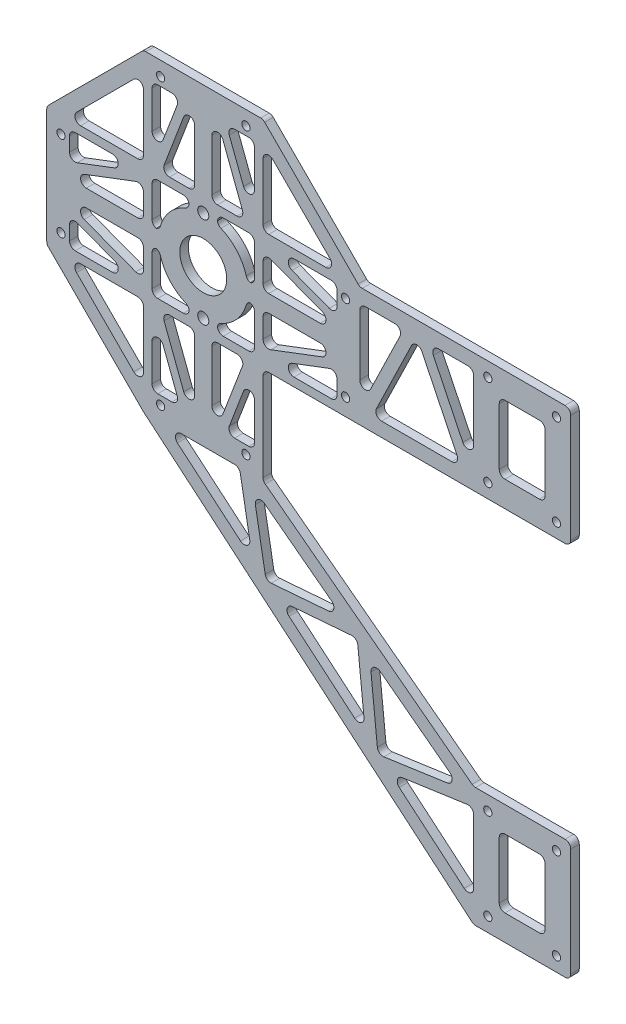
SolidWorks part; units mm, degrees
material "Thornel Mat VMA"
ref_plane "前视基准面" through (0, 0, 0) normal (0, 0, 1) x (1, 0, 0)
ref_plane "上视基准面" through (0, 0, 0) normal (0, 1, 0) x (1, 0, 0)
ref_plane "右视基准面" through (0, 0, 0) normal (1, 0, 0) x (0, 0, -1)
other "Configuration Table"
sketch "草图1" plane through (0, 0, 0) normal (0, 0, 1) x (1, 0, 0)
  line L0 (100, -1053.4194) -> (100, 48946.5806) construction
  line L1 (124.12, -1022.8771) -> (124.12, 48977.1229) construction
  line L2 (0, -1000) -> (0, 49000) construction
  line L3 (0, 16) -> (124.12, 16) construction
  line L4 (124.12, -16) -> (0, -16) construction
  line L6 (-15, 21) -> (129.12, 21) construction
  line L7 (-15, 21) -> (-15, -21) construction
  line L8 (-15, -21) -> (129.12, -21) construction
  line L9 (129.12, 21) -> (129.12, -21) construction
  line L18 (-1000, 50) -> (49000, 50) construction
  line L19 (-1000, -50) -> (49000, -50) construction
  line L20 (-50, -995.7067) -> (-50, 49004.2933) construction
  line L21 (50, -1002.265) -> (50, 48997.735) construction
  line L22 (0, 0) -> (15, 50) construction
  line L23 (100, -116) -> (124.12, -116) construction
  line L24 (100, -148) -> (124.12, -148) construction
  line L25 (21, 55) -> (-21, 55) construction
  line L26 (-55, 21) -> (-15, 21) construction
  line L27 (-55, 21) -> (-55, -21) construction
  line L28 (-55, -21) -> (-15, -21) construction
  line L29 (-15, 21) -> (-15, -21) construction
  line L30 (21, 55) -> (21, 15) construction
  line L31 (21, 15) -> (-21, 15) construction
  line L32 (-21, 55) -> (-21, 15) construction
  line L33 (55, -21) -> (55, 21) construction
  line L34 (55, -21) -> (15, -21) construction
  line L35 (15, -21) -> (15, 21) construction
  line L36 (55, 21) -> (15, 21) construction
  line L37 (-21, -55) -> (21, -55) construction
  line L38 (-21, -55) -> (-21, -15) construction
  line L39 (-21, -15) -> (21, -15) construction
  line L40 (21, -55) -> (21, -15) construction
  line L41 (0, 0) -> (-15, 21) construction
  line L42 (-55, 21) -> (-55, -21)
  line L43 (-55, -21) -> (-21, -55)
  line L44 (-21, -55) -> (95, -153)
  line L45 (95, -153) -> (129.12, -153)
  line L46 (129.12, -153) -> (129.12, 21)
  line L47 (129.12, 21) -> (55, 21)
  line L48 (55, 21) -> (21, 55)
  line L49 (21, 55) -> (-21, 55)
  line L50 (-21, 55) -> (-55, 21)
  circle A0 centre (0, 0) radius 16 construction
  circle A1 centre (0, 16) radius 1.95
  circle A2 centre (0, -16) radius 1.95
  circle A3 centre (0, 0) radius 8.25
  circle A4 centre (100, 16) radius 1.45
  circle A5 centre (100, -16) radius 1.45
  circle A6 centre (124.12, -16) radius 1.45
  circle A7 centre (124.12, 16) radius 1.45
  circle A8 centre (-15, 50) radius 1.45
  circle A9 centre (15, 50) radius 1.45
  circle A10 centre (50, 15) radius 1.45
  circle A11 centre (50, -15) radius 1.45
  circle A12 centre (15, -50) radius 1.45
  circle A13 centre (-15, -50) radius 1.45
  circle A14 centre (-50, -15) radius 1.45
  circle A15 centre (-50, 15) radius 1.45
  circle A16 centre (100, -116) radius 1.45
  circle A17 centre (124.12, -116) radius 1.45
  circle A18 centre (100, -148) radius 1.45
  circle A19 centre (124.12, -148) radius 1.45
  dimension "D1" = 3.9
  dimension "D2" = 32
  dimension "D3" = 16.5
  dimension "D6" = 2.9
  dimension "D7" = 15
  dimension "D17" = 4
  dimension "D15" = 2.9
  dimension "D16" = 30
  dimension "D4" = 100
  dimension "D5" = 24.12
  dimension "D8" = 5
  dimension "D9" = 5
  dimension "D10" = 5
  dimension "D11" = 50
  dimension "D12" = 50
  dimension "D13" = 50
  dimension "D14" = 50
  dimension "D18" = 32
  dimension "D19" = 100
  dimension "D20" = 5
  dimension "D22" = 5
  dimension "D23" = 5
  dimension "D21" = 4
extrude "凸台-拉伸1" add sketch "草图1" along normal blind 3
sketch "草图2" plane through (0, 0, 3) normal (0, 0, 1) x (1, 0, 0)
  line L0 (-21, 55) -> (-21, -55) construction
  line L1 (-55, -21) -> (129.12, -21) construction
  line L2 (129.12, -153) -> (129.12, 21) construction
  line L3 (127.917, 21) -> (-55, 21) construction
  line L4 (21, 55) -> (21, -55) construction
  line L5 (21, -55) -> (-21, -55) construction
  line L6 (129.12, -111) -> (95, -111) construction
  line L7 (95, -111) -> (95, -153) construction
  line L8 (95, -111) -> (95, -21) construction
  line L9 (21, -55) -> (95, -111) construction
  line L10 (129.12, -21) -> (21, -21)
  line L11 (21, -21) -> (21, -55)
  line L12 (21, -55) -> (95, -111)
  line L13 (95, -111) -> (129.12, -111)
  line L14 (129.12, -111) -> (129.12, -21)
  line L15 (-47.9289, -21) -> (-21, -47.9289)
  line L16 (-21, -47.9289) -> (-21, -21)
  line L17 (-21, -21) -> (-47.9289, -21)
  line L18 (-55, -21) -> (-21, -55) construction
  line L19 (-21, 21) -> (-21, 47.9289)
  line L20 (-21, 47.9289) -> (-47.9289, 21)
  line L21 (-47.9289, 21) -> (-21, 21)
  line L22 (21, 21) -> (47.9289, 21)
  line L23 (47.9289, 21) -> (21, 47.9289)
  line L24 (21, 47.9289) -> (21, 21)
  line L25 (0, 0) -> (-21, -21) construction
  line L26 (0, 0) -> (-21, 21) construction
  line L27 (-55, 0) -> (-21, 0) construction
  line L28 (-55, 21) -> (-55, -21) construction
  line L35 (-47, -8.1113) -> (-47, -18)
  line L36 (-47, -18) -> (-21, -18)
  line L37 (-21, -18) -> (-47, -8.1113)
  line L38 (-21, -14.7903) -> (-52, -3)
  line L39 (-52, -3) -> (-21, -3)
  line L40 (-21, -3) -> (-21, -14.7903)
  line L41 (-52, 3) -> (-21, 3)
  line L42 (-21, 14.7903) -> (-52, 3)
  line L43 (-21, 3) -> (-21, 14.7903)
  line L44 (-47, 18) -> (-21, 18)
  line L45 (-47, 8.1113) -> (-47, 18)
  line L46 (-21, 18) -> (-47, 8.1113)
  line L47 (18, 47) -> (18, 21)
  line L48 (18, 21) -> (8.1113, 47)
  line L49 (8.1113, 47) -> (18, 47)
  line L50 (3, 52) -> (3, 21)
  line L51 (3, 21) -> (14.7903, 21)
  line L52 (14.7903, 21) -> (3, 52)
  line L53 (-3, 21) -> (-14.7903, 21)
  line L54 (-14.7903, 21) -> (-3, 52)
  line L55 (-3, 52) -> (-3, 21)
  line L56 (-18, 21) -> (-8.1113, 47)
  line L57 (-8.1113, 47) -> (-18, 47)
  line L58 (-18, 47) -> (-18, 21)
  line L59 (47, -18) -> (21, -18)
  line L60 (21, -18) -> (47, -8.1113)
  line L61 (47, -8.1113) -> (47, -18)
  line L62 (52, -3) -> (21, -3)
  line L63 (21, -3) -> (21, -14.7903)
  line L64 (21, -14.7903) -> (52, -3)
  line L65 (21, 3) -> (21, 14.7903)
  line L66 (21, 14.7903) -> (52, 3)
  line L67 (52, 3) -> (21, 3)
  line L68 (21, 18) -> (47, 8.1113)
  line L69 (47, 8.1113) -> (47, 18)
  line L70 (47, 18) -> (21, 18)
  line L71 (-18, -47) -> (-18, -21)
  line L72 (-18, -21) -> (-8.1113, -47)
  line L73 (-8.1113, -47) -> (-18, -47)
  line L74 (-3, -52) -> (-3, -21)
  line L75 (-3, -21) -> (-14.7903, -21)
  line L76 (-14.7903, -21) -> (-3, -52)
  line L77 (3, -21) -> (14.7903, -21)
  line L78 (14.7903, -21) -> (3, -52)
  line L79 (3, -52) -> (3, -21)
  line L80 (18, -21) -> (8.1113, -47)
  line L81 (8.1113, -47) -> (18, -47)
  line L82 (18, -47) -> (18, -21)
  line L83 (55, 21) -> (55, -21) construction
  line L84 (-13.2523, -55) -> (95, -146.4545) construction
  line L85 (12.7142, -55) -> (95, -117.2703) construction
  line L86 (-21, -55) -> (95, -153) construction
  line L87 (12.7142, -55) -> (-13.2523, -55)
  line L88 (-13.2523, -55) -> (17.3031, -80.8141)
  line L89 (17.3031, -80.8141) -> (12.7142, -55)
  line L90 (17.4084, -58.5524) -> (22.0838, -84.8529)
  line L91 (22.0838, -84.8529) -> (49.3047, -82.6901)
  line L92 (49.3047, -82.6901) -> (17.4084, -58.5524)
  line L93 (26.4252, -88.5206) -> (54.1032, -86.3214)
  line L94 (54.1032, -86.3214) -> (56.9806, -114.3347)
  line L95 (56.9806, -114.3347) -> (26.4252, -88.5206)
  line L96 (58.4632, -89.6208) -> (61.3837, -118.0545)
  line L97 (61.3837, -118.0545) -> (90.5115, -113.8736)
  line L98 (90.5115, -113.8736) -> (58.4632, -89.6208)
  line L99 (65.4723, -121.5087) -> (95, -117.2703)
  line L100 (95, -117.2703) -> (95, -146.4545)
  line L101 (95, -146.4545) -> (65.4723, -121.5087)
  line L102 (100, -116) -> (100, -148) construction
  line L103 (100, -148) -> (124.12, -148) construction
  line L104 (124.12, -148) -> (124.12, -116) construction
  line L105 (124.12, -116) -> (100, -116) construction
  line L106 (120.12, -120) -> (104, -120)
  line L107 (104, -120) -> (104, -144)
  line L108 (104, -144) -> (120.12, -144)
  line L109 (120.12, -144) -> (120.12, -120)
  line L110 (100, 16) -> (100, -16) construction
  line L111 (100, -16) -> (124.12, -16) construction
  line L112 (124.12, -16) -> (124.12, 16) construction
  line L113 (124.12, 16) -> (100, 16) construction
  line L114 (120.12, 12) -> (104, 12)
  line L115 (104, 12) -> (104, -12)
  line L116 (104, -12) -> (120.12, -12)
  line L117 (120.12, -12) -> (120.12, 12)
  line L118 (95, -21) -> (95, 21) construction
  line L119 (55, 16) -> (95, 16) construction
  line L120 (55, -16) -> (95, -16) construction
  line L121 (55, 16) -> (55, -16)
  line L122 (55, -16) -> (70.5526, 16)
  line L123 (70.5526, 16) -> (55, 16)
  line L124 (75, 16) -> (59.4474, -16)
  line L125 (59.4474, -16) -> (90.5526, -16)
  line L126 (90.5526, -16) -> (75, 16)
  line L127 (79.4474, 16) -> (95, -16)
  line L128 (95, -16) -> (95, 16)
  line L129 (95, 16) -> (79.4474, 16)
  line L130 (-5, 18) -> (-5, 14.9229)
  line L131 (-18, 18) -> (-5, 18)
  line L132 (-18, 18) -> (-18, 3)
  line L133 (-18, -18) -> (-5, -18)
  line L134 (18, 18) -> (18, 3)
  line L135 (-18, 18) -> (18, -18) construction
  line L136 (-18, -18) -> (18, 18) construction
  line L137 (-5, 14.9229) -> (5, 14.9229) construction
  line L138 (5, 14.9229) -> (5, 18)
  line L139 (5, 18) -> (18, 18)
  line L140 (-5, -14.9229) -> (-5, -18)
  line L141 (5, -18) -> (18, -18)
  line L142 (5, -14.9229) -> (5, -18)
  line L143 (-18, 3) -> (-15.4497, 3)
  line L144 (15.4497, 3) -> (18, 3)
  line L145 (18, -3) -> (15.4497, -3)
  line L146 (-15.4497, -3) -> (-18, -3)
  line L147 (-18, -3) -> (-18, -18)
  line L148 (18, -3) -> (18, -18)
  line L149 (129.12, 21) -> (55, 21) construction
  circle A0 centre (124.12, -116) radius 1.45 construction
  arc A1 (-5, 14.9229) -> (-15.4497, 3) centre (0, 0) ccw
  circle A2 centre (-50, -15) radius 1.45 construction
  arc A3 (5, -14.9229) -> (15.4497, -3) centre (0, 0) ccw
  circle A4 centre (0, 16) radius 1.95 construction
  arc A5 (15.4497, 3) -> (5, 14.9229) centre (0, 0) ccw
  arc A6 (-15.4497, -3) -> (-5, -14.9229) centre (0, 0) ccw
  point P169 (127.917, 21)
  dimension "D7" = 3
  dimension "D8" = 3
  dimension "D27" = 5
  dimension "D29" = 15.7383
  dimension "D1" = 5
  dimension "D2" = 5
  dimension "D4" = 90
  dimension "D5" = 3
  dimension "D6" = 3
  dimension "D9" = 3
  dimension "D11" = 5
  dimension "D12" = 5
  dimension "D13" = 4
  dimension "D14" = 4
  dimension "D15" = 40
  dimension "D16" = 40
  dimension "D17" = 40
  dimension "D18" = 4
  dimension "D19" = 4
  dimension "D22" = 5
  dimension "D23" = 5
  dimension "D24" = 4
  dimension "D25" = 4
  dimension "D26" = 3
  dimension "D28" = 36
  dimension "D20" = 4
  dimension "D21" = 4
  dimension "D3" = 3
  dimension "D10" = 4
extrude "切除-拉伸1" cut sketch "草图2" against normal through all
fillet "圆角1" radius 2 123 edges at (21, -55, 1.5) (21, -21, 1.5) (129.12, -21, 1.5) (129.12, 21, 1.5) (55, 21, 1.5) (21, 55, 1.5) (-21, 55, 1.5) (-55, 21, 1.5) (-55, -21, 1.5) (-21, -55, 1.5) (95, -153, 1.5) (129.12, -153, 1.5) (129.12, -111, 1.5) (95, -111, 1.5) (3, -21, 1.5) (14.7903, -21, 1.5) (3, -52, 1.5) (18, -21, 1.5) (18, -47, 1.5) (8.1113, -47, 1.5) (-18, -21, 1.5) (-8.1113, -47, 1.5) (-3, -21, 1.5) (-3, -52, 1.5) (-14.7903, -21, 1.5) (61.3837, -118.0545, 1.5) (58.4632, -89.6208, 1.5) (90.5115, -113.8736, 1.5) (54.1032, -86.3214, 1.5) (56.9806, -114.3347, 1.5) (26.4252, -88.5206, 1.5) (22.0838, -84.8529, 1.5) (17.4084, -58.5524, 1.5) (49.3047, -82.6901, 1.5) (95, -117.2703, 1.5) (95, -146.4545, 1.5) (65.4723, -121.5087, 1.5) (59.4474, -16, 1.5) (75, 16, 1.5) (90.5526, -16, 1.5) (95, -16, 1.5) (79.4474, 16, 1.5) (95, 16, 1.5) (55, -16, 1.5) (55, 16, 1.5) (70.5526, 16, 1.5) (104, -12, 1.5) (104, 12, 1.5) (120.12, 12, 1.5) (120.12, -12, 1.5) (104, -144, 1.5) (104, -120, 1.5) (120.12, -120, 1.5) (120.12, -144, 1.5) (-52, -3, 1.5) (-21, -3, 1.5) (-21, -14.7903, 1.5) (-18, 21, 1.5) (-18, 47, 1.5) (-8.1113, 47, 1.5) (-21, 18, 1.5) (-47, 8.1113, 1.5) (-47, 18, 1.5) (-21, 3, 1.5) (-52, 3, 1.5) (-21, 14.7903, 1.5) (-21, -47.9289, 1.5) (-47.9289, -21, 1.5) (-21, -21, 1.5) (-21, 21, 1.5) (-47.9289, 21, 1.5) (-21, 47.9289, 1.5) (21, 21, 1.5) (21, 47.9289, 1.5) (47.9289, 21, 1.5) (-47, -18, 1.5) (-47, -8.1113, 1.5) (-21, -18, 1.5) (3, 21, 1.5) (3, 52, 1.5) (14.7903, 21, 1.5) (18, 21, 1.5) (8.1113, 47, 1.5) (18, 47, 1.5) (-3, 21, 1.5) (-14.7903, 21, 1.5) (-3, 52, 1.5) (12.7142, -55, 1.5) (17.3031, -80.8141, 1.5) (-13.2523, -55, 1.5) (21, 3, 1.5) (21, 14.7903, 1.5) (52, 3, 1.5) (21, 18, 1.5) (47, 18, 1.5) (47, 8.1113, 1.5) (21, -18, 1.5) (47, -8.1113, 1.5) (47, -18, 1.5) (21, -3, 1.5) (52, -3, 1.5) (21, -14.7903, 1.5) (-18, -47, 1.5) (18, 3, 1.5) (15.4497, 3, 1.5) (5, 14.9229, 1.5) (5, 18, 1.5) (18, 18, 1.5) (5, -18, 1.5) (5, -14.9229, 1.5) (15.4497, -3, 1.5) (18, -3, 1.5) (18, -18, 1.5) (-18, 3, 1.5) (-18, 18, 1.5) (-5, 18, 1.5) (-5, 14.9229, 1.5) (-15.4497, 3, 1.5) (-15.4497, -3, 1.5) (-5, -14.9229, 1.5) (-5, -18, 1.5) (-18, -3, 1.5) (-18, -18, 1.5)
